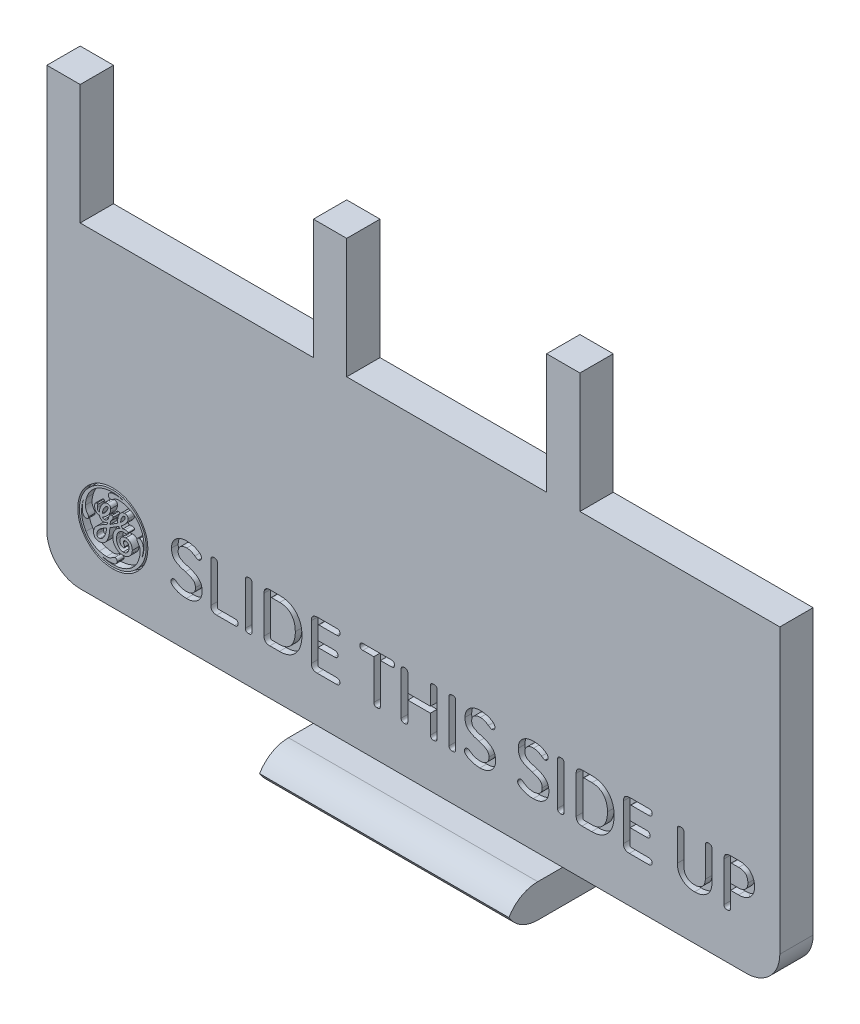
SolidWorks part; units mm, degrees
ref_plane "FRONT" through (0, 0, 0) normal (0, 0, 1) x (1, 0, 0)
ref_plane "TOP" through (0, 0, 0) normal (0, 1, 0) x (1, 0, 0)
ref_plane "RIGHT" through (0, 0, 0) normal (1, 0, 0) x (0, 0, -1)
sketch "Sketch2" plane through (0, 0, 0) normal (0, 0, 1) x (1, 0, 0)
  line L0 (-39.3226, 14.1694) -> (-39.3226, -19.1277)
  line L1 (1.3174, 5.0254) -> (1.3174, 14.1694)
  line L3 (-39.3226, -19.1277) -> (16.5574, -19.1277)
  line L6 (16.5574, 5.0254) -> (1.3174, 5.0254)
  line L7 (1.3174, 14.1694) -> (-1.2226, 14.1694)
  line L8 (-1.2226, 14.1694) -> (-1.2226, 5.0254)
  line L9 (-1.2226, 5.0254) -> (-16.4626, 5.0254)
  line L10 (-16.4626, 5.0254) -> (-16.4626, 14.1694)
  line L11 (-16.4626, 14.1694) -> (-19.0026, 14.1694)
  line L12 (-19.0026, 14.1694) -> (-19.0026, 5.0254)
  line L13 (-38.0526, 5.0254) -> (-19.0026, 5.0254)
  line L14 (-38.0526, 5.0254) -> (-38.0526, 14.1694)
  line L15 (-38.0526, 14.1694) -> (-39.3226, 14.1694)
  line L16 (16.5574, 5.0254) -> (16.5574, -19.1277)
  point P1 (0, 0)
  point P2 (0, 0)
  point P5 (-39.3952, -19.0953)
extrude "Boss-Extrude1" add sketch "Sketch2" along normal blind 1.27 and the other way blind 1.27 contours L3 L16 L6 L1 L7 L8 L9 L10 L11 L12 L13 L14 L15 L0
sketch "Sketch3" plane through (0, -19.1277, 0) normal (0, -1, 0) x (1, 0, 0)
  line L12 (0, -50) -> (0, 50) construction
  line L17 (-19.0071, 5.7057) -> (0, 5.7057)
  line L18 (-19.0071, 5.7057) -> (-19.0071, -4.9844)
  line L19 (-19.0071, -4.9844) -> (0, -4.9844)
  line L20 (0, 5.7057) -> (0, -4.9844)
extrude "Boss-Extrude2" add sketch "Sketch3" along normal blind 2.54
fillet "Fillet2" radius 2.54 4 edges at (-9.5035, -19.1277, -4.9844) (-9.5035, -21.6677, -4.9844) (-9.5035, -19.1277, 5.7057) (-9.5035, -21.6677, 5.7057)
sketch "Sketch5" plane through (0, 0, 1.27) normal (0, 0, 1) x (1, 0, 0)
  text T0 "SLIDE THIS SIDE UP" font "GE Inspira Medium" height in points 14
extrude "Cut-Extrude1" cut sketch "Sketch5" against normal blind 0.508
sketch "Sketch6" plane through (0, 0, 1.27) normal (0, 0, 1) x (1, 0, 0)
  text T0 "g" font "GELogoFont" height in points 20
extrude "Cut-Extrude3" cut sketch "Sketch6" against normal blind 0.508
fillet "Fillet3" radius 2.54 2 edges at (16.5574, -19.1277, 0) (-39.3226, -19.1277, 0)
sketch "Sketch7" plane through (-38.0526, 0, 0) normal (1, 0, 0) x (0, 0, -1)
  line L1 (-1.27, 14.1694) -> (1.27, 14.1694)
  line L2 (-1.27, 14.1694) -> (-1.27, 5.0254)
  line L3 (-1.27, 5.0254) -> (1.27, 5.0254)
  line L4 (1.27, 14.1694) -> (1.27, 5.0254)
sketch "Sketch9" plane through (-38.0526, 0, 0) normal (1, 0, 0) x (0, 0, -1)
  line L1 (-1.27, 14.1694) -> (1.27, 14.1694)
  line L2 (-1.27, 14.1694) -> (-1.27, 5.0254)
  line L3 (-1.27, 5.0254) -> (1.27, 5.0254)
  line L4 (1.27, 14.1694) -> (1.27, 5.0254)
extrude "Boss-Extrude3" add sketch "Sketch9" along normal blind 1.27
